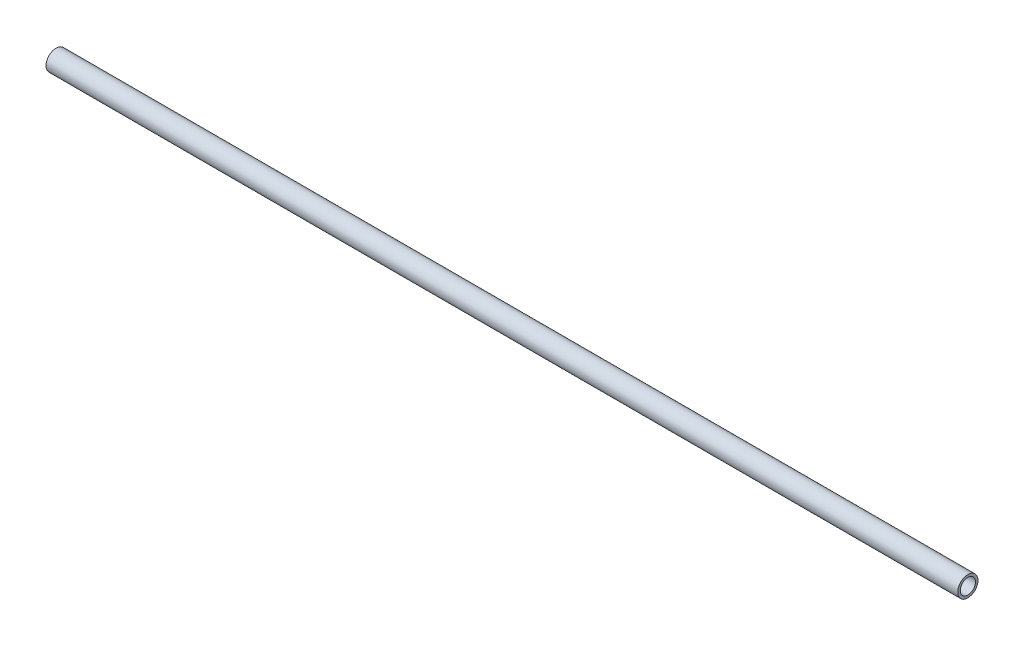
SolidWorks part; units mm, degrees
ref_plane "Front Plane" through (0, 0, 0) normal (0, 0, 1) x (1, 0, 0)
ref_plane "Top Plane" through (0, 0, 0) normal (0, 1, 0) x (1, 0, 0)
ref_plane "Right Plane" through (0, 0, 0) normal (1, 0, 0) x (0, 0, -1)
ref_axis "Axis1" through (-4.5, 0, 0) along (1, 0, 0)
sketch "Sketch1" plane through (0, 0, 0) normal (1, 0, 0) x (0, 0, -1)
  circle A0 centre (0, 0) radius 0.75
  circle A1 centre (0, 0) radius 1
  dimension "D1" = 1.5
  dimension "D2" = 2
extrude "Boss-Extrude1" add sketch "Sketch1" along normal blind 90
sketch "Sketch2" plane through (0, 0, 0) normal (-1, 0, 0) x (0, 0, 1)
  line L0 (0, 0) -> (0, 0.6106) construction
  line L2 (-0.304, 0.6106) -> (-0.304, 1.0992)
  line L3 (-0.304, 1.0992) -> (0.304, 1.0992)
  line L4 (0.304, 1.0992) -> (0.304, 0.6106)
  arc A0 (-0.304, 0.6106) -> (0.304, 0.6106) centre (0, 0.6106) ccw
  dimension "D1" = 0.608
extrude "Cut-Extrude1" [suppressed] cut sketch "Sketch2" against normal blind 1
sketch "Sketch3" plane through (0, 0, 0) normal (0, 0, 1) x (1, 0, 0)
  circle A0 centre (0.7986, 0) radius 0.3969
  dimension "D1" = 0.7937
extrude "Cut-Extrude2" cut sketch "Sketch3" against normal blind 10
equation "\"Do\"=8.5mm"
equation "\"Lo\"=10"
equation "\"screw_diam\" = 3.5mm"
equation "\"wheel_Do\"=12.5mm"
equation "\"wheel_thickness\"=4mm"
equation "\"Collet_diameter\"=4.3"
equation "\"clearance\"= 0.5mm"
equation "\"handle_body_width\" = 10mm"
equation "\"finger_diameter\"=35"
equation "\"collet_lid_diameter\"=10"
equation "\"screw_cap_diam\"=5.15"
equation "\"handle_thickness\"=12.5mm"
equation "\"post_hole_diam\"=2"
equation "\"roll_rod_diam\"= 6.5 "
equation "\"roll_rod_length\"=6.6"
equation "\"disc_diam\"=5"
equation "\"disc_width\"=1.5"
equation "\"arm_width\"=5"
equation "\"arm_thickness\"=4.5"
equation "\"wheel_total_diam\"=30"
equation "\"spring_diam\"=4.1"
equation "\"collet_length\" = 18.75mm"
equation "\"tip_length\" = 40mm"
equation "\"cable_tube_OD\"=0.508"
equation "\"D1@Sketch2\"=\"cable_tube_OD\"+0.1"
